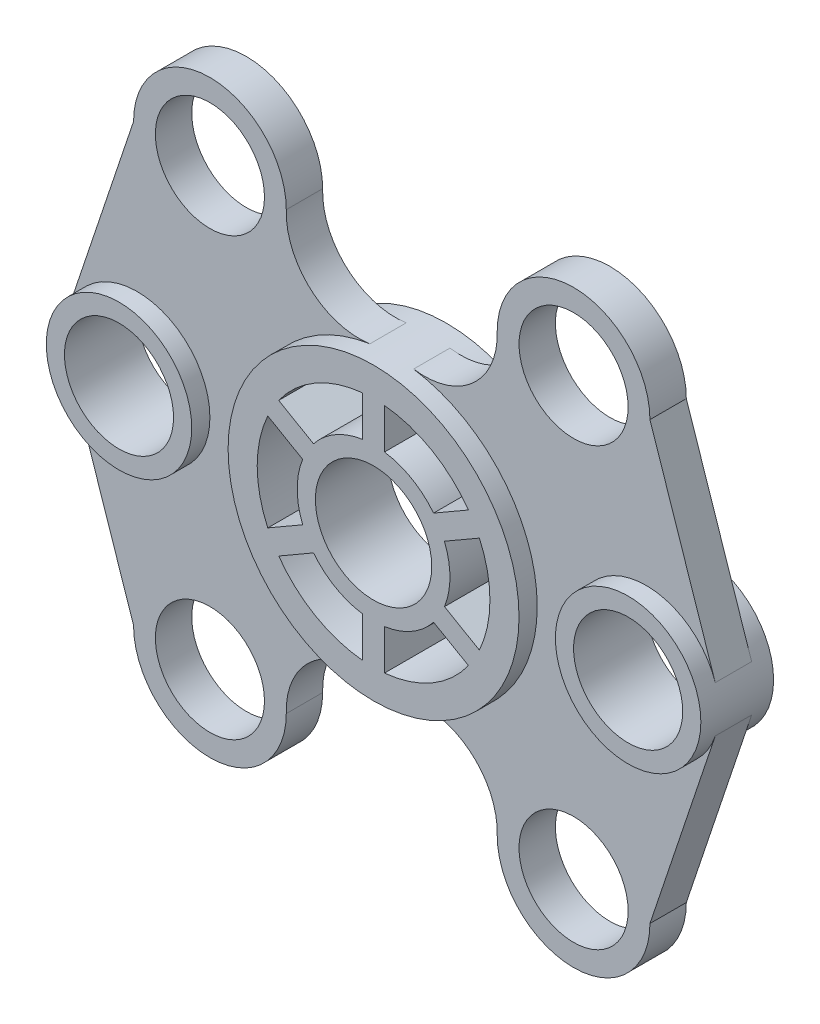
SolidWorks part; units mm, degrees
ref_plane "Front Plane" through (0, 0, 0) normal (0, 0, 1) x (1, 0, 0)
ref_plane "Top Plane" through (0, 0, 0) normal (0, 1, 0) x (1, 0, 0)
ref_plane "Right Plane" through (0, 0, 0) normal (1, 0, 0) x (0, 0, -1)
sketch "Sketch1" plane through (0, 0, 0) normal (0, 0, 1) x (1, 0, 0)
  line L0 (0, 30.9599) -> (0, -32.3995) construction
  line L1 (-3, 20.7846) -> (-3, 31.8591)
  line L2 (3, 20.7846) -> (3, 31.8591)
  line L3 (16.5, 12.9904) -> (26.0908, 18.5276)
  line L4 (19.5, 7.7942) -> (29.0908, 13.3315)
  line L5 (19.5, -7.7942) -> (29.0908, -13.3315)
  line L6 (16.5, -12.9904) -> (26.0908, -18.5276)
  line L7 (3, -20.7846) -> (3, -31.8591)
  line L8 (-3, -20.7846) -> (-3, -31.8591)
  line L9 (-16.5, -12.9904) -> (-26.0908, -18.5276)
  line L10 (-19.5, -7.7942) -> (-29.0908, -13.3315)
  line L11 (-19.5, 7.7942) -> (-29.0908, 13.3315)
  line L12 (-16.5, 12.9904) -> (-26.0908, 18.5276)
  line L13 (0, 0) -> (-50000, 0) construction
  line L14 (-71, -60) -> (-88.965, -6.3506)
  line L15 (71, -60) -> (88.965, -6.3506)
  line L16 (71, 60) -> (88.965, 6.3506)
  line L17 (-71, 60) -> (-88.965, 6.3506)
  arc A0 (-3, 31.8591) -> (-26.0908, 18.5276) centre (0, 0) ccw
  arc A2 (-3, 20.7846) -> (-16.5, 12.9904) centre (0, 0) ccw
  arc A3 (-19.5, 7.7942) -> (-19.5, -7.7942) centre (0, 0) ccw
  arc A4 (-29.0908, 13.3315) -> (-29.0908, -13.3315) centre (0, 0) ccw
  arc A5 (-16.5, -12.9904) -> (-3, -20.7846) centre (0, 0) ccw
  arc A6 (-26.0908, -18.5276) -> (-3, -31.8591) centre (0, 0) ccw
  arc A7 (3, -31.8591) -> (26.0908, -18.5276) centre (0, 0) ccw
  arc A8 (3, -20.7846) -> (16.5, -12.9904) centre (0, 0) ccw
  arc A9 (29.0908, -13.3315) -> (29.0908, 13.3315) centre (0, 0) ccw
  arc A10 (19.5, -7.7942) -> (19.5, 7.7942) centre (0, 0) ccw
  arc A11 (26.0908, 18.5276) -> (3, 31.8591) centre (0, 0) ccw
  arc A12 (16.5, 12.9904) -> (3, 20.7846) centre (0, 0) ccw
  circle A13 centre (0, 0) radius 16
  circle A14 centre (0, 0) radius 40
  circle A15 centre (-70, 0) radius 15
  arc A16 (-88.965, 6.3506) -> (-88.965, -6.3506) centre (-70, 0) ccw
  circle A19 centre (-50, -60) radius 15
  circle A21 centre (50, -60) radius 15
  circle A22 centre (70, 0) radius 15
  circle A23 centre (70, 0) radius 20
  circle A24 centre (50, 60) radius 15
  circle A25 centre (-50, 60) radius 15
  arc A26 (-71, -60) -> (-29, -60) centre (-50, -60) ccw
  arc A27 (-29, -60) -> (-6.0077, -39.5463) centre (-9.0116, -59.3194) cw
  arc A28 (71, -60) -> (29, -60) centre (50, -60) cw
  arc A29 (29, -60) -> (6.0077, -39.5463) centre (9.0116, -59.3194) ccw
  arc A30 (71, 60) -> (29, 60) centre (50, 60) ccw
  arc A31 (29, 60) -> (6.0077, 39.5463) centre (9.0116, 59.3194) cw
  arc A32 (-29, 60) -> (-6.0077, 39.5463) centre (-9.0116, 59.3194) ccw
  arc A33 (-71, 60) -> (-29, 60) centre (-50, 60) cw
  circle A34 centre (-70, 0) radius 20
  point P34 (0, 0)
  dimension "D1" = 32
  dimension "D2" = 21
  dimension "D3" = 32
  dimension "D7" = 80
  dimension "D8" = 30
  dimension "D9" = 40
  dimension "D10" = 20
  dimension "D13" = 30
  dimension "D14" = 42
  dimension "D15" = 20
  dimension "D4" = 6
  dimension "D5" = 3
  dimension "D11" = 50
  dimension "D12" = 60
  dimension "D6" = 6
extrude "Boss-Extrude1" add sketch "Sketch1" along normal mid plane 20 contours A16 A34 A15 | A23 A22 | A14 L3 A12 L2 A11 L5 A10 L4 A9 L7 A8 L6 A7 L1 A2 L12 A0 A4 L11 A3 L10 A6 L9 A5 L8 A13 region at (-89.4343, 0, 0) region at (-38.8686, 0, 0) region at (50.5657, 0, 0)
extrude "Boss-Extrude2" add sketch "Sketch1<4>" along normal mid plane 10 contours A34 L14 A26 A27 A14 A32 A33 L17 A19 A25 | A30 A31 A14 A29 A28 L15 A23 L16 A24 A21 region at (-78.2566, -32.5974, 0) region at (31.7143, -27.2602, 0)
sketch "Sketch1<4>" plane through (0, 0, 0) normal (0, 0, 1) x (1, 0, 0) same geometry as "Sketch1"
